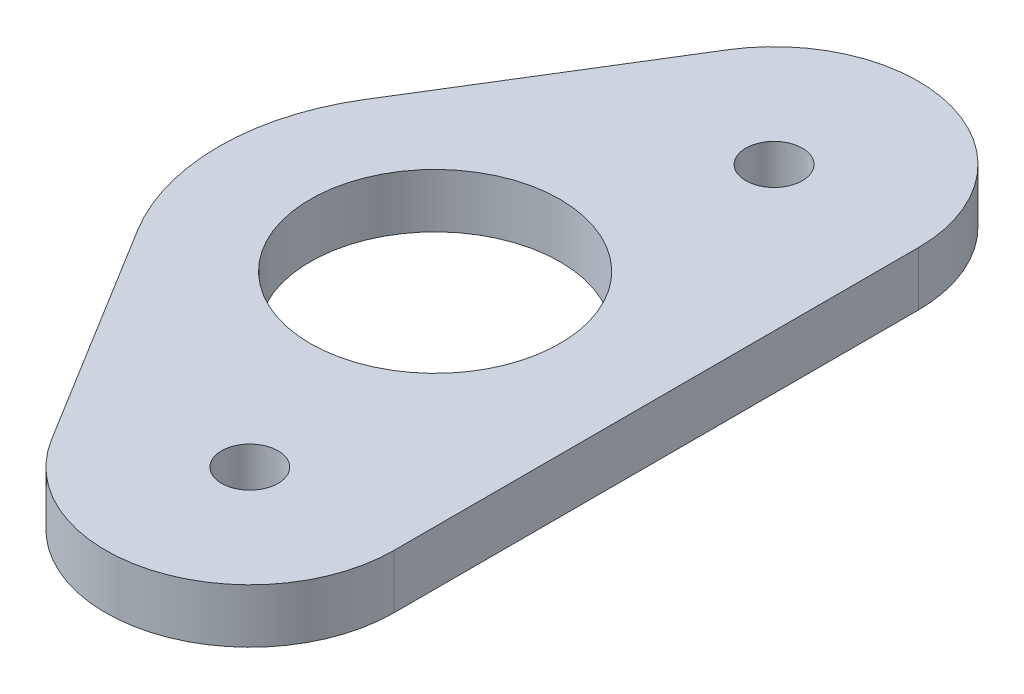
SolidWorks part; units mm, degrees
material "6061-T6 (SS)"
ref_plane "Front Plane" through (0, 0, 0) normal (0, 0, 1) x (1, 0, 0)
ref_plane "Top Plane" through (0, 0, 0) normal (0, 1, 0) x (1, 0, 0)
ref_plane "Right Plane" through (0, 0, 0) normal (1, 0, 0) x (0, 0, -1)
sketch "Sketch1" plane through (0, 0, 0) normal (0, 1, 0) x (1, 0, 0)
  line L0 (-62.5, 0) -> (0, 0) construction
  line L1 (-55.733, 23.0854) -> (0, 0) construction
  line L2 (0, 0) -> (-55.733, -23.0854) construction
  line L3 (-78.718, 9.994) -> (-66.545, 29.748)
  line L4 (-43.033, 23.0854) -> (-43.033, -23.0854)
  line L6 (-66.545, -29.748) -> (-78.718, -9.994)
  circle A0 centre (-62.5, 0) radius 11
  circle A1 centre (-55.733, 23.0854) radius 2.4892
  circle A2 centre (-55.733, -23.0854) radius 2.4892
  circle A3 centre (-55.733, 23.0854) radius 12.7
  circle A4 centre (-62.5, 0) radius 19.05
  circle A5 centre (-55.733, -23.0854) radius 12.7
  dimension "D1" = 22
  dimension "D5" = 4.9784
  dimension "D6" = 38.1
  dimension "D7" = 25.4
  dimension "D2" = 62.5
  dimension "D3" = 60.325
  dimension "D4" = 22.5
extrude "Boss-Extrude1" add sketch "Sketch1" along normal blind 4.7625 contours A5 A4 A2 | A5 A4 L6 | A4 A5 | A5 A4 A3 A0 | A3 A4 | A4 A3 A1 | A5 L4 A3 A4 | A4 A3 L3 region at (-73.6019, 0, -14.8244) region at (-71.0284, 0, -19.6459) region at (-52.364, 0, -34.9744) region at (-71.0284, 0, 19.6459) region at (-58.1778, 0, -14.7451) region at (-43.0795, 0, 0) region at (-68.0443, 0, 24.1484) region at (-58.1778, 0, 14.7451)
